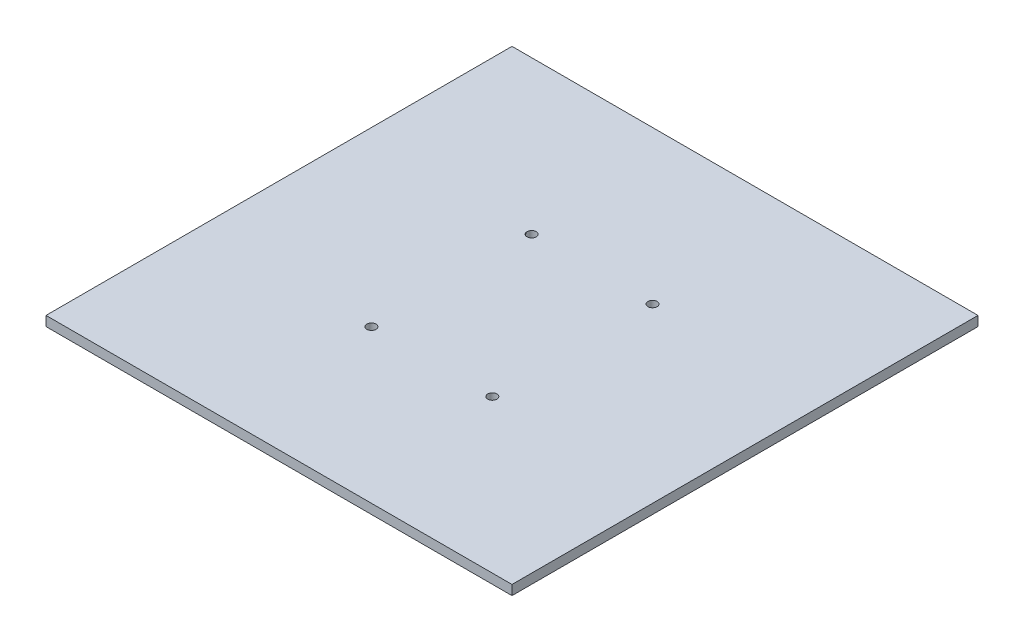
SolidWorks part; units mm, degrees
material "Thornel Mat VMA"
ref_plane "Front Plane" through (0, 0, 0) normal (0, 0, 1) x (1, 0, 0)
ref_plane "Top Plane" through (0, 0, 0) normal (0, 1, 0) x (1, 0, 0)
ref_plane "Right Plane" through (0, 0, 0) normal (1, 0, 0) x (0, 0, -1)
sketch "Sketch1" plane through (0, 0, 0) normal (0, 1, 0) x (1, 0, 0)
  line L1 (-76.2, -76.2) -> (76.2, -76.2)
  line L2 (-76.2, -76.2) -> (-76.2, 76.2)
  line L3 (-76.2, 76.2) -> (76.2, 76.2)
  line L4 (76.2, -76.2) -> (76.2, 76.2)
  line L5 (-76.2, -76.2) -> (76.2, 76.2) construction
  line L6 (-76.2, 76.2) -> (76.2, -76.2) construction
  point P0 (0, 0)
  dimension "D1" = 152.4
  dimension "D2" = 152.4
extrude "Boss-Extrude1" add sketch "Sketch1" along normal blind 3.175
sketch "Sketch2" plane through (0, 3.175, 0) normal (0, 1, 0) x (1, 0, 0)
  circle A0 centre (19.7711, -26.1938) radius 1.5 construction
  circle A1 centre (19.7711, 26.1937) radius 1.5 construction
  circle A2 centre (-19.7711, -26.1938) radius 1.5 construction
  circle A3 centre (-19.7711, 26.1937) radius 1.5 construction
  circle A4 centre (19.7711, -26.1938) radius 1.5
  circle A5 centre (19.7711, 26.1937) radius 1.5
  circle A6 centre (-19.7711, -26.1938) radius 1.5
  circle A7 centre (-19.7711, 26.1937) radius 1.5
extrude "Cut-Extrude1" cut sketch "Sketch2" against normal through all
equation "\"D2@Sketch1\"=\"D1@Sketch1\""
